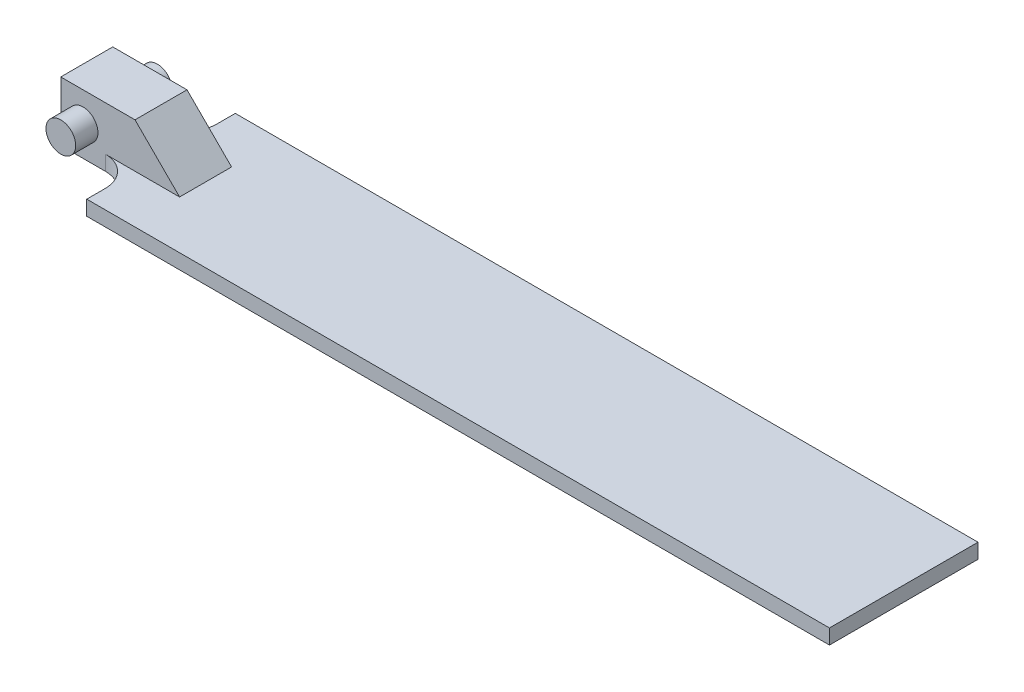
SolidWorks part; units mm, degrees
ref_plane "Front Plane" through (0, 0, 0) normal (0, 0, 1) x (1, 0, 0)
ref_plane "Top Plane" through (0, 0, 0) normal (0, 1, 0) x (1, 0, 0)
ref_plane "Right Plane" through (0, 0, 0) normal (1, 0, 0) x (0, 0, -1)
sketch "Sketch2" plane through (0, 0, 0) normal (0, 1, 0) x (1, 0, 0)
  line L1 (0, -3.5) -> (10, -3.5)
  line L2 (0, -3.5) -> (0, 3.5)
  line L3 (0, 3.5) -> (10, 3.5)
  line L4 (10, -3.5) -> (10, 3.5)
  point P4 (0, 0)
  dimension "D1" = 7
  dimension "D2" = 10
extrude "Boss-Extrude1" add sketch "Sketch2" along normal blind 8
sketch "Sketch3" plane through (0, 0, 3.5) normal (0, 0, 1) x (1, 0, 0)
  line L0 (3.01, 2) -> (3.01, 0) construction
  line L1 (0, 0) -> (10, 0) construction
  line L3 (1.01, 4) -> (0, 4) construction
  line L6 (0, 8) -> (0, 0) construction
  circle A0 centre (3.01, 4) radius 2
  point P6 (0, 4)
  dimension "D2" = 4
  dimension "D1" = 2
  dimension "D3" = 1.01
extrude "Boss-Extrude2" add sketch "Sketch3" along normal blind 3
mirror "Mirror1" about plane through (0, 0, 0) normal (0, 0, 1) of "Boss-Extrude2"
sketch "Sketch4" plane through (10, 0, 0) normal (1, 0, 0) x (0, 0, -1)
  line L1 (-10, 0) -> (10, 0)
  line L2 (-10, 0) -> (-10, 2)
  line L3 (-10, 2) -> (10, 2)
  line L4 (10, 0) -> (10, 2)
  point P4 (0, 0)
  dimension "D1" = 20
  dimension "D2" = 2
extrude "Boss-Extrude3" add sketch "Sketch4" along normal blind 100
chamfer "Chamfer1" distance 6 angle 45 1 edges at (10, 2, 0)
fillet "Fillet1" radius 4 2 edges at (10, 1, -3.5) (10, 1, 3.5)
